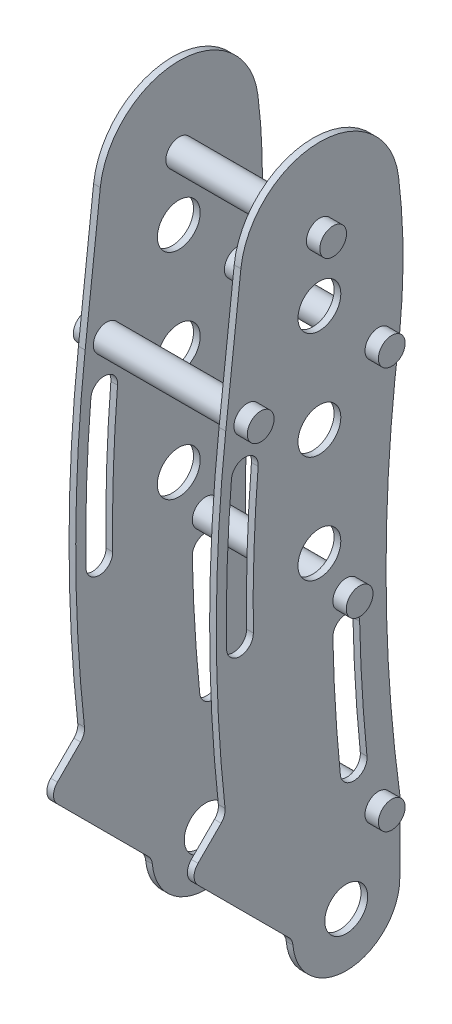
SolidWorks part; units mm, degrees
material "3.0505 (EN-AW 3105)"
ref_plane "Płaszczyzna przednia" through (0, 0, 0) normal (0, 0, 1) x (1, 0, 0)
ref_plane "Płaszczyzna górna" through (0, 0, 0) normal (0, 1, 0) x (1, 0, 0)
ref_plane "Płaszczyzna prawa" through (0, 0, 0) normal (1, 0, 0) x (0, 0, -1)
sketch "Szkic1" plane through (0, 0, 0) normal (1, 0, 0) x (0, 0, -1)
  line L0 (20, 0) -> (20, 26.9952)
  line L1 (-20, 0) -> (-58.8909, 38.8909)
  line L2 (0, -20) -> (-164.9058, -20) construction
  line L3 (-58.8909, 38.8909) -> (-45, 52.7817)
  line L4 (-39.3506, 226.7051) -> (-45, 176.9952)
  circle A0 centre (0, 0) radius 8
  arc A1 (20, 0) -> (-20, 0) centre (0, 0) cw
  arc A2 (20, 26.9952) -> (20, 176.9952) centre (564.8624, 101.9952) cw
  arc A3 (-45, 52.7817) -> (-45, 176.9952) centre (501.4822, 114.8885) cw
  arc A4 (20, 176.9952) -> (19.5436, 226.9952) centre (-198.7939, 200) ccw
  arc A5 (19.5436, 226.9952) -> (-39.3506, 226.7051) centre (-9.8863, 223.3565) ccw
  point P15 (0, 0)
  point P18 (0, 0)
  point P19 (0, 0)
  dimension "D1" = 16
  dimension "D2" = 20
  dimension "D3" = 550
  dimension "D6" = 550
  dimension "D10" = 220
  dimension "D12" = 200
  dimension "D4" = 150
  dimension "D5" = 26.9952
  dimension "D7" = 45
  dimension "D8" = 55
  dimension "D9" = 65
  dimension "D11" = 50
extrude "Dodanie-wyciągnięcie1" add sketch "Szkic1" along normal blind 27.5 and the other way blind 27.5
sketch "Szkic2" plane through (0, 0, 0) normal (0, 0, 1) x (1, 0, 0)
  line L0 (-27.5, -20) -> (27.5, -20) construction
  line L1 (-25, -20) -> (25, -20)
  line L2 (-25, -20) -> (-25, 251.0105)
  line L4 (25, -20) -> (25, 251.0105)
  line L6 (-27.5, 176.9952) -> (-27.5, 52.7817) construction
  line L7 (27.5, 52.7817) -> (27.5, 176.9952) construction
  line L8 (-25, 251.0105) -> (25, 251.0105)
  line L9 (27.5, 253.0105) -> (-27.5, 253.0105) construction
  dimension "D1" = 2.5
  dimension "D2" = 2.5
  dimension "D3" = 2
extrude "Wytnij-wyciągnięcie3" cut sketch "Szkic2" against normal through all both and the other way through all contours L2 L8 L4 L1
sketch "Szkic3" plane through (27.5, 0, 0) normal (1, 0, 0) x (0, 0, -1)
  line L0 (20, 0) -> (20, 26.9952) construction
  line L1 (-39.3506, 226.7051) -> (-45, 176.9952) construction
  circle A0 centre (12, 26.9952) radius 5
  circle A1 centre (0, 101.9952) radius 5
  circle A2 centre (20.8865, 235) radius 5
  circle A3 centre (-36.9485, 176.9952) radius 5
  arc A4 (20, 176.9952) -> (20, 26.9952) centre (564.8624, 101.9952) ccw construction
  point P12 (14.8624, 101.9952)
  dimension "D1" = 10
  dimension "D2" = 10
  dimension "D3" = 10
  dimension "D4" = 10
  dimension "D6" = 560
  dimension "D5" = 8
  dimension "D7" = 235
  dimension "D8" = 8
sketch "Szkic4" plane through (0, 0, 0) normal (1, 0, 0) x (0, 0, -1)
  circle A0 centre (12, 26.9952) radius 5 construction
  circle A1 centre (0, 101.9952) radius 5 construction
  circle A3 centre (-36.9485, 176.9952) radius 5 construction
  circle A4 centre (12, 26.9952) radius 5
  circle A5 centre (0, 101.9952) radius 5
  circle A6 centre (12, 176.9952) radius 5
  circle A7 centre (-36.9485, 176.9952) radius 5
  circle A8 centre (-9.8863, 223.3565) radius 5
  arc A9 (19.5436, 226.9952) -> (-39.3506, 226.7051) centre (-9.8863, 223.3565) ccw construction
  point P4 (0, 0)
  point P5 (12, 176.9952)
  point P17 (0, 0)
  point P18 (20.8865, 235)
  point P20 (0, 0)
  dimension "D1" = 10
extrude "Dodanie-wyciągnięcie2" add sketch "Szkic4" along normal blind 32.5 and the other way blind 32.5
sketch "Szkic5" plane through (0, 0, 0) normal (0, 0, 1) x (1, 0, 0)
  line L0 (27.5, 253.0105) -> (-27.5, 253.0105) construction
  line L1 (-25, 251.0105) -> (25, 251.0105)
  line L2 (-25, 251.0105) -> (-25, 253.0105)
  line L3 (-25, 253.0105) -> (25, 253.0105)
  line L4 (25, 251.0105) -> (25, 253.0105)
  line L5 (25, 251.0105) -> (25, 226.7051) construction
extrude "Wytnij-wyciągnięcie4" cut sketch "Szkic5" against normal through all both and the other way through all
sketch "Szkic7" plane through (27.5, 0, 0) normal (1, 0, 0) x (0, 0, -1)
  circle A0 centre (-10.0324, 200) radius 8
  circle A1 centre (-10.0324, 160) radius 8
  circle A2 centre (-10.0324, 120) radius 8
  arc A5 (19.5436, 226.9952) -> (-39.3506, 226.7051) centre (-9.8863, 223.3565) ccw construction
  arc A6 (-39.7046, 106.5058) -> (-37.8863, 160) centre (501.4822, 114.8885) cw construction
  arc A7 (-42.8689, 160.4167) -> (-44.704, 106.4284) centre (501.4822, 114.8885) ccw
  arc A8 (-32.9037, 159.5833) -> (-34.7052, 106.5833) centre (501.4822, 114.8885) ccw
  arc A9 (-32.9037, 159.5833) -> (-42.8689, 160.4167) centre (-37.8863, 160) ccw
  arc A10 (-44.704, 106.4284) -> (-34.7052, 106.5833) centre (-39.7046, 106.5058) ccw
  arc A11 (-45, 176.9952) -> (-45, 52.7817) centre (501.4822, 114.8885) ccw construction
  arc A12 (0, 90.4018) -> (2.7632, 45) centre (564.8624, 101.9952) ccw construction
  arc A18 (-4.9989, 90.2992) -> (-2.2113, 44.4956) centre (564.8624, 101.9952) ccw
  arc A19 (4.9989, 90.5044) -> (7.7377, 45.5044) centre (564.8624, 101.9952) ccw
  arc A20 (4.9989, 90.5044) -> (-4.9989, 90.2992) centre (0, 90.4018) ccw
  arc A21 (-2.2113, 44.4956) -> (7.7377, 45.5044) centre (2.7632, 45) ccw
  arc A22 (20, 176.9952) -> (20, 26.9952) centre (564.8624, 101.9952) ccw construction
  point P8 (0, 0)
  point P9 (-38.6293, 150)
  point P10 (-39.4571, 133.2754)
  point P14 (-10.0324, 253.0101)
  point P27 (0.9245, 67.6731)
  dimension "D1" = 16
  dimension "D7" = 10
  dimension "D8" = 8.7484
  dimension "D9" = 53
  dimension "D6" = 10
  dimension "D10" = 45
  dimension "D2" = 40
  dimension "D3" = 40
  dimension "D4" = 120
  dimension "D11" = 45
extrude "Wytnij-wyciągnięcie5" cut sketch "Szkic7" against normal through all
fillet "Zaokrąglenie1" radius 5 8 edges at (-26.25, 26.9952, -20) (26.25, 26.9952, -20) (-26.25, 0, 20) (26.25, 0, 20) (-26.25, 52.7817, 45) (26.25, 52.7817, 45) (-26.25, 38.8909, 58.8909) (26.25, 38.8909, 58.8909)
